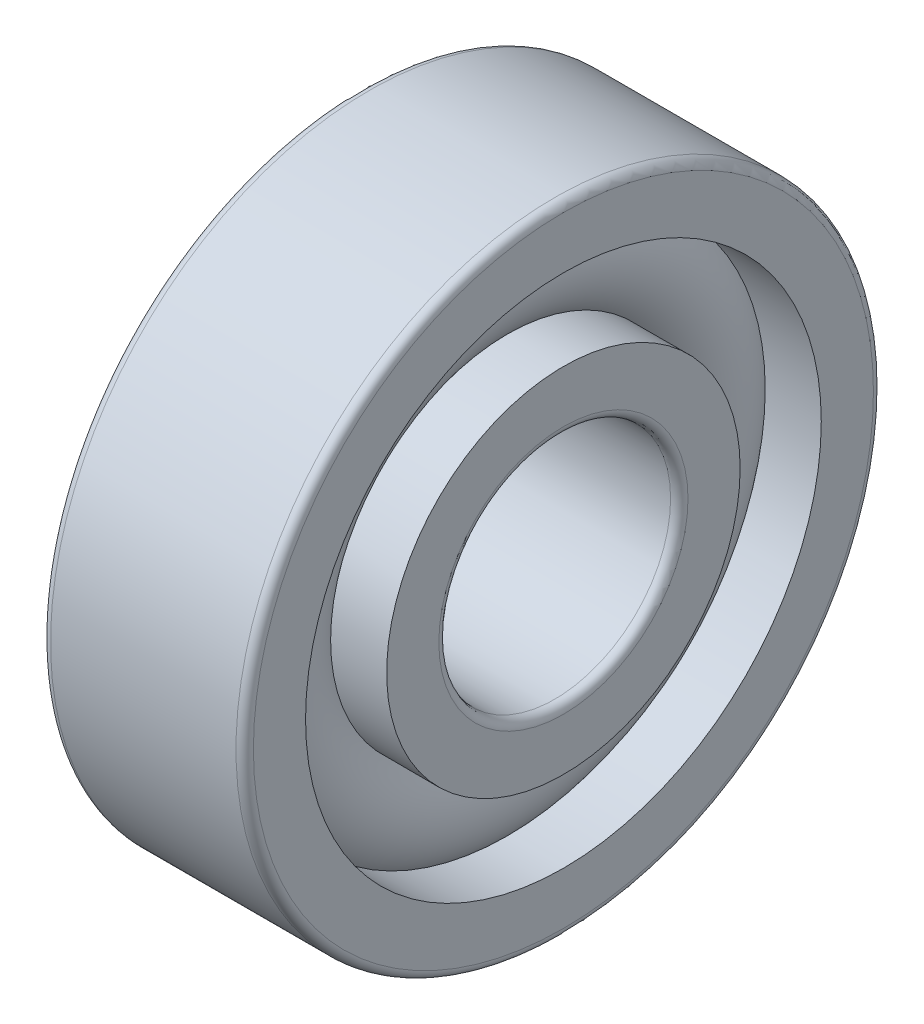
SolidWorks part; units mm, degrees
ref_plane "Plane1" through (0, 0, 0) normal (0, 0, 1) x (1, 0, 0)
ref_plane "Plane2" through (0, 0, 0) normal (0, 1, 0) x (1, 0, 0)
ref_plane "Plane3" through (0, 0, 0) normal (1, 0, 0) x (0, 0, -1)
other "Configuration Table"
sketch "Clipboard" plane through (0, 0, 0) normal (0, 0, 1) x (1, 0, 0)
  line L0 (-10, 0) -> (10, 0) construction
  line L1 (0, 0) -> (22.3471, -0.7804)
  line L2 (0, 0) -> (7.4954, 0.2617)
  line L3 (0, 0) -> (22.3471, -0.7804)
  line L4 (0, 0) -> (-22.3573, -0.3902)
sketch "CagSpiSke" plane through (0, 0, 0) normal (0, 0, 1) x (1, 0, 0)
  line L0 (0.21, 7.15) -> (0.21, 7.85)
  line L1 (0.21, 7.85) -> (-0.21, 7.85)
  line L2 (-0.21, 7.85) -> (-0.21, 7.15)
  line L3 (-0.21, 7.15) -> (0.21, 7.15)
  line L4 (-20.6375, 0) -> (20.6375, 0) construction
  line L5 (0, 0) -> (0, 23.7692) construction
revolve "CageSpine" add sketch "CagSpiSke" angle 0.001 about L4 reverse direction yes
ref_axis "Axis1" through (-50, 0, 0) along (1, 0, 0)
sketch "CagBalSke" plane through (0, 0, 0) normal (0, 0, 1) x (1, 0, 0)
  line L0 (-2.31, 7.5) -> (2.31, 7.5)
  line L1 (-1.905, 7.5) -> (1.905, 7.5) construction
  line L2 (-10, 0) -> (10, 0) construction
  line L3 (0, 0) -> (0, 24) construction
  arc A0 (2.31, 7.5) -> (-2.31, 7.5) centre (0, 7.5) cw
revolve "CageBall" [suppressed] add sketch "CagBalSke" angle 360 about L1 reverse direction yes
pattern_circular "CageBalls" [suppressed] count 2 every 180 about axis through (-50, 0, 0) along (1, 0, 0)
sketch "CagTrmODSke" plane through (0, 0, 0) normal (0, 0, 1) x (1, 0, 0)
  line L0 (2.311, 7.85) -> (2.311, 9.811)
  line L1 (2.311, 9.811) -> (-2.311, 9.811)
  line L2 (-2.311, 9.811) -> (-2.311, 7.85)
  line L3 (-2.311, 7.85) -> (2.311, 7.85)
  line L4 (-20.6375, 0) -> (20.6375, 0) construction
  line L5 (0, 0) -> (0, 25) construction
revolve "CageTrimOD" [suppressed] cut sketch "CagTrmODSke" angle 360 about L4 reverse direction yes
sketch "CagTrmIDSke" plane through (0, 0, 0) normal (0, 0, 1) x (1, 0, 0)
  line L0 (2.311, 5.191) -> (2.311, 7.15)
  line L1 (2.311, 7.15) -> (-2.311, 7.15)
  line L2 (-2.311, 7.15) -> (-2.311, 5.191)
  line L3 (-2.311, 5.191) -> (2.311, 5.191)
  line L4 (-20.6375, 0) -> (20.6375, 0) construction
  line L5 (0, 0) -> (0, 25) construction
revolve "CageTrimID" [suppressed] cut sketch "CagTrmIDSke" angle 360 about L4 reverse direction yes
sketch "BalSimSke" plane through (0, 0, 0) normal (0, 0, 1) x (1, 0, 0)
  line L0 (-10, 0) -> (10, 0) construction
  line L1 (-10, 7.5) -> (10, 7.5) construction
  line L2 (0, 0) -> (0, 23) construction
  circle A0 centre (0, 7.5) radius 2.1
revolve "BallsSimplified" add sketch "BalSimSke" angle 360 about L0
sketch "BalDetSke" plane through (0, 0, 0) normal (0, 0, 1) x (1, 0, 0)
  line L0 (-2.1, 7.5) -> (2.1, 7.5)
  line L1 (-1.905, 7.5) -> (1.905, 7.5) construction
  line L2 (0, 0) -> (0, 25) construction
  arc A0 (2.1, 7.5) -> (-2.1, 7.5) centre (0, 7.5) cw
revolve "BallDetailed" [suppressed] add sketch "BalDetSke" angle 360 about L1 reverse direction yes
sketch "InnRacSke" plane through (0, 0, 0) normal (0, 0, 1) x (1, 0, 0)
  line L0 (-1.5315, 6.1) -> (-3.5, 6.1)
  line L1 (-3.5, 6.1) -> (-3.5, 4.3)
  line L2 (-3.2, 4) -> (3.2, 4)
  line L3 (3.5, 4.3) -> (3.5, 6.1)
  line L4 (3.5, 6.1) -> (1.5315, 6.1)
  line L5 (-20.6375, 0) -> (20.6375, 0) construction
  line L6 (0, 0) -> (0, 30) construction
  arc A0 (-3.5, 4.3) -> (-3.2, 4) centre (-3.2, 4.3) ccw
  arc A1 (3.2, 4) -> (3.5, 4.3) centre (3.2, 4.3) ccw
  arc A2 (1.5315, 6.1) -> (-1.5315, 6.1) centre (0, 7.5) cw
  dimension "Fillet_radius" = 0.3
revolve "InnerRace" add sketch "InnRacSke" angle 360 about L5 reverse direction yes
sketch "OutRacSke" plane through (0, 0, 0) normal (0, 0, 1) x (1, 0, 0)
  line L0 (-1.5315, 8.9) -> (-3.5, 8.9)
  line L1 (-3.5, 8.9) -> (-3.5, 10.7)
  line L2 (-3.2, 11) -> (3.2, 11)
  line L3 (3.5, 10.7) -> (3.5, 8.9)
  line L4 (3.5, 8.9) -> (1.5315, 8.9)
  line L5 (-20.6375, 0) -> (20.6375, 0) construction
  line L6 (0, 0) -> (0, 30) construction
  arc A0 (-3.5, 10.7) -> (-3.2, 11) centre (-3.2, 10.7) cw
  arc A1 (3.2, 11) -> (3.5, 10.7) centre (3.2, 10.7) cw
  arc A2 (1.5315, 8.9) -> (-1.5315, 8.9) centre (0, 7.5) ccw
  dimension "Fillet_radius" = 0.3
revolve "OuterRace" add sketch "OutRacSke" angle 360 about L5 reverse direction yes
pattern_circular "BallsDetailed" [suppressed] count 2 every 180 about axis through (-50, 0, 0) along (1, 0, 0)
equation "\"BallCLRad@Clipboard\" = ( \"OD@OutRacSke\" + \"ID@InnRacSke\" ) / 4"
equation "\"BallCLRad@BalSimSke\" = \"BallCLRad@Clipboard\""
equation "\"BallCLRad@BalDetSke\" = \"BallCLRad@Clipboard\""
equation "\"BallCLRad@InnRacSke\" = \"BallCLRad@Clipboard\""
equation "\"BallCLRad@OutRacSke\" = \"BallCLRad@Clipboard\""
equation "\"Ball_diameter@InnRacSke\" = \"Ball_diameter@BalDetSke\" - 0.05"
equation "\"Ball_diameter@OutRacSke\" = \"Ball_diameter@BalDetSke\" - 0.05"
equation "\"Ball_diameter@BalSimSke\" = \"Ball_diameter@BalDetSke\""
equation "\"Width@OutRacSke\" = \"Width@InnRacSke\""
equation "\"Fillet_radius@OutRacSke\" = \"Fillet_radius@InnRacSke\""
equation "\"Max_count@Clipboard\" = int( 3.14159265 / atn(( \"Ball_diameter@BalDetSke\" / 2) / sqr( \"BallCLRad@Clipboard\"  *  \"BallCLRad@Clipboard\" - ( \"Ball_diameter@BalDetSke\" / 2) *  ( \"Ball_diameter@BalDetSke\" / 2))))"
equation "\"Max_count@Clipboard\" = ((sgn( \"Max_count@Clipboard\" - \"Count@Clipboard\" )-1)*( \"Max_count@Clipboard\" - \"Count@Clipboard\" ))/-2+ \"Count@Clipboard\""
equation "\"Count@BallsDetailed\" = int( \"Show_count@Clipboard\" ) "
equation "\"Count@BallsDetailed\" = ((sgn( \"Count@BallsDetailed\" - \"Max_count@Clipboard\" )-1)*( \"Count@BallsDetailed\" - \"Max_count@Clipboard\" ))/-2+ \"Max_count@Clipboard\""
equation "\"Count@BallsDetailed\" = ((sgn( \"Count@BallsDetailed\" - \"Min_count@Clipboard\" )+1)*( \"Count@BallsDetailed\" - \"Min_count@Clipboard\"))/2 +\"Min_count@Clipboard\""
equation "\"Angle@BallsDetailed\" = 360.0 / \"Max_count@Clipboard\""
equation "\"BallCLRad@CagBalSke\" = \"BallCLRad@Clipboard\""
equation "\"Count@CageBalls\" = \"Count@BallsDetailed\""
equation "\"Angle@CageBalls\" = \"Angle@BallsDetailed\""
equation "\"Angle@CageSpine\" =  \"Angle@CageBalls\" * ( \"Count@CageBalls\" -1 + int( \"Count@CageBalls\" / \"Max_count@Clipboard\" ) )  + 0.001 -  int( \"Count@CageBalls\" / \"Max_count@Clipboard\" ) * 0.001"
equation "\"Angle@CageSpine\" =  \"Angle@CageSpine\" * int( \"Min_count@Clipboard\" / 2) + int(1 / \"Min_count@Clipboard\")  * 0.001"
equation "\"CageWallOD@CagBalSke\" =  \"Ball_diameter@BalDetSke\" * 1.1"
equation "\"Thickness@CagSpiSke\" =  \"Ball_diameter@BalDetSke\" * 0.1"
equation "\"OD@CagTrmODSke\" = \"BallCLRad@Clipboard\" * 2 + \"CageWallOD@CagBalSke\" + 0.002"
equation "\"ID@CagTrmODSke\" = \"BallCLRad@Clipboard\" * 2 + \"Ball_diameter@BalDetSke\" / 6"
equation "\"OD@CagTrmIDSke\" = \"BallCLRad@Clipboard\" * 2 - \"Ball_diameter@BalDetSke\" / 6"
equation "\"ID@CagTrmIDSke\" = \"BallCLRad@Clipboard\" * 2 - \"CageWallOD@CagBalSke\" + 0.002"
equation "\"OD@CagSpiSke\" = \"ID@CagTrmODSke\""
equation "\"ID@CagSpiSke\" = \"OD@CagTrmIDSke\""
equation "\"Width@CagTrmODSke\" = \"CageWallOD@CagBalSke\" + 0.002"
equation "\"Width@CagTrmIDSke\" = \"CageWallOD@CagBalSke\" + 0.002"
